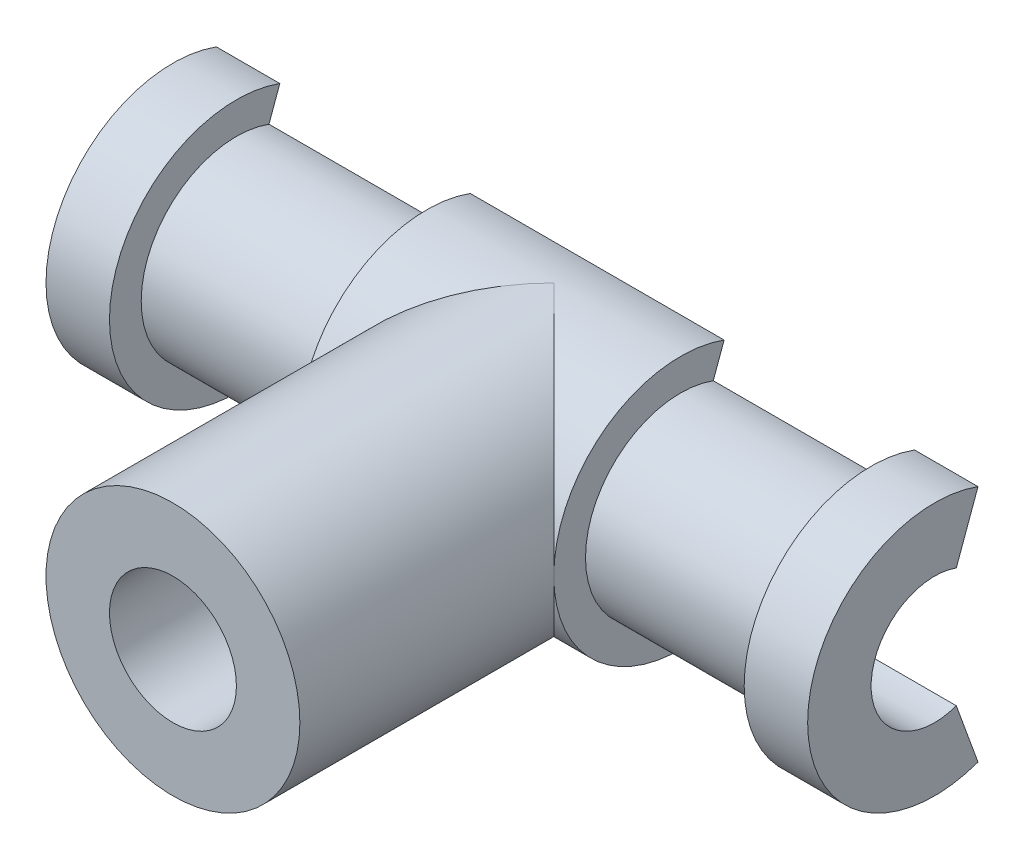
SolidWorks part; units mm, degrees
ref_plane "Front Plane" through (0, 0, 0) normal (0, 0, 1) x (1, 0, 0)
ref_plane "Top Plane" through (0, 0, 0) normal (0, 1, 0) x (1, 0, 0)
ref_plane "Right Plane" through (0, 0, 0) normal (1, 0, 0) x (0, 0, -1)
sketch "Sketch1" plane through (0, 0, 0) normal (0, 0, 1) x (1, 0, 0)
  circle A0 centre (0, 0) radius 1.5875
  circle A1 centre (0, 0) radius 3.175
  dimension "D1" = 3.175
  dimension "D2" = 1.5875
extrude "Boss-Extrude1" add sketch "Sketch1" along normal blind 9.525
sketch "Sketch2" plane through (0, 0, 0) normal (0, 1, 0) x (1, 0, 0)
  line L0 (0, 0) -> (-9.525, 0)
  line L1 (3.175, 0) -> (-3.175, 0) construction
  dimension "D1" = 9.525
ref_plane "Plane1" through (-9.525, 0, 0) normal (-1, 0, 0) x (0, 0, 1)
sketch "Sketch3" plane through (-9.525, 0, 0) normal (-1, 0, 0) x (0, 0, 1)
  line L0 (-1.0859, -2.9835) -> (-0.543, -1.4918)
  line L1 (-0.543, 1.4918) -> (-1.0859, 2.9835)
  line L2 (0, 0) -> (0, 3.175) construction
  line L3 (0, 0) -> (0, -3.175) construction
  line L4 (0, 0) -> (-0.543, 1.4918) construction
  line L5 (-0.543, -1.4918) -> (0, 0) construction
  arc A0 (-1.0859, 2.9835) -> (-1.0859, -2.9835) centre (0, 0) cw
  arc A1 (-0.543, -1.4918) -> (-0.543, 1.4918) centre (0, 0) ccw
  dimension "D1" = 20
  dimension "D2" = 3.175
  dimension "D4" = 1.5875
  dimension "D3" = 20
extrude "Boss-Extrude2" add sketch "Sketch3" against normal blind 19.05
sketch "Sketch4" plane through (-9.525, 0, 0) normal (-1, 0, 0) x (0, 0, 1)
  circle A0 centre (0, 0) radius 1.5875
extrude "Cut-Extrude1" cut sketch "Sketch4" against normal through all
ref_plane "Plane2" through (0, 0, 0) normal (1, 0, 0) x (0, 0, -1)
sketch "Sketch5" plane through (0, 0, 0) normal (1, 0, 0) x (0, 0, -1)
  circle A0 centre (0, 0) radius 3.175
  circle A1 centre (0, 0) radius 2.3812
  arc A2 (1.0859, 2.9835) -> (1.0859, -2.9835) centre (0, 0) ccw construction
  dimension "D1" = 0.7937
extrude "Cut-Extrude2" cut sketch "Sketch5" against normal blind 4.7625 from offset 3.175 offset against normal yes
mirror "Mirror1" about plane through (0, 0, 0) normal (1, 0, 0) of "Cut-Extrude2"
